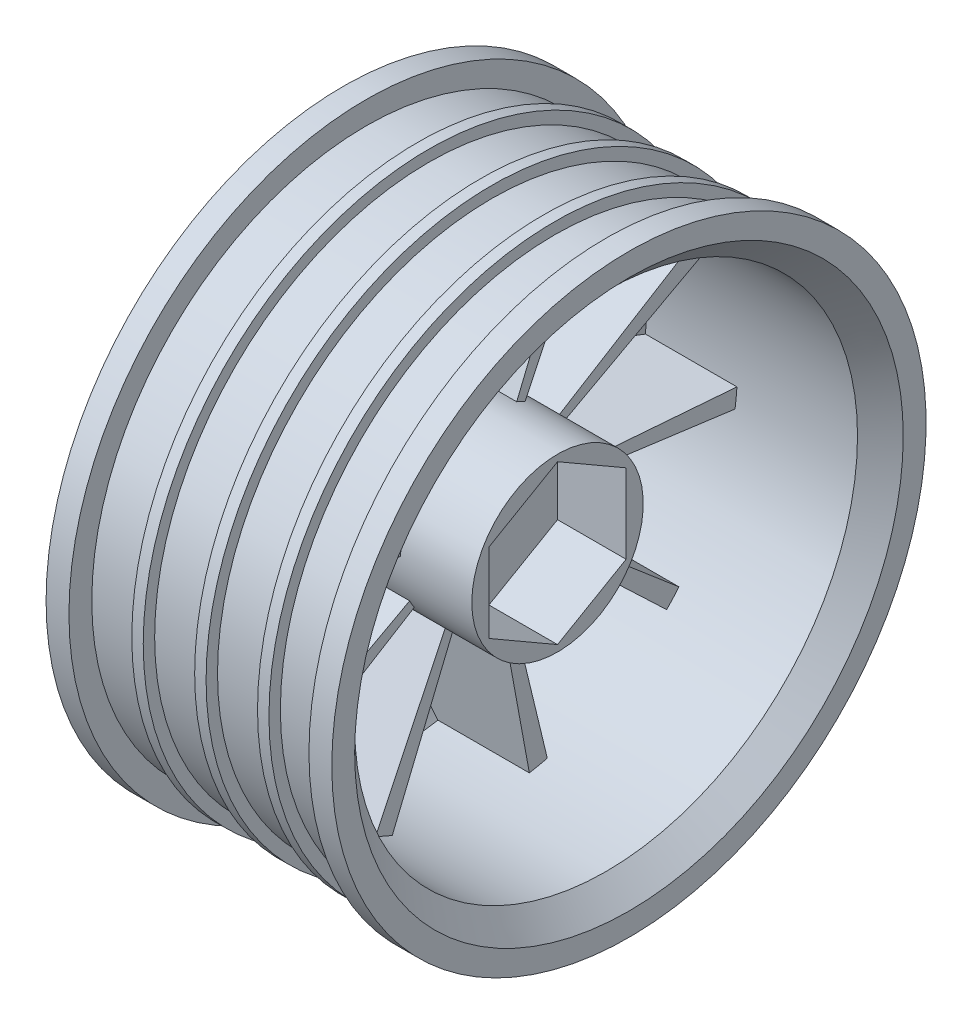
SolidWorks part; units mm, degrees
ref_plane "Front Plane" through (0, 0, 0) normal (0, 0, 1) x (1, 0, 0)
ref_plane "Top Plane" through (0, 0, 0) normal (0, 1, 0) x (1, 0, 0)
ref_plane "Right Plane" through (0, 0, 0) normal (1, 0, 0) x (0, 0, -1)
sketch "Sketch1" plane through (0, 0, 0) normal (0, 1, 0) x (1, 0, 0)
  line L0 (0, 26) -> (-2, 26)
  line L1 (-2, 26) -> (-2, 24)
  line L2 (-2, 24) -> (-6.5, 24)
  line L3 (-6.5, 24) -> (-6.5, 25)
  line L4 (-6.5, 25) -> (-7.5, 25)
  line L5 (-7.5, 25) -> (-7.5, 24)
  line L6 (-7.5, 24) -> (-12, 24)
  line L7 (-12, 24) -> (-12, 25)
  line L8 (-12, 25) -> (-13, 25)
  line L9 (-13, 25) -> (-13, 24)
  line L10 (-13, 24) -> (-17.5, 24)
  line L11 (-17.5, 24) -> (-17.5, 25)
  line L12 (-17.5, 25) -> (-18.5, 25)
  line L13 (-18.5, 25) -> (-18.5, 24)
  line L14 (-18.5, 24) -> (-23, 24)
  line L15 (-23, 24) -> (-23, 26)
  line L16 (-23, 26) -> (-25, 26)
  line L17 (-25, 26) -> (-25, 20)
  line L18 (0, 26) -> (0, 24)
  line L19 (0, 24) -> (-2, 22)
  line L20 (-2, 22) -> (-12.5, 22)
  line L21 (-12.5, 22) -> (-12.5, 7.5)
  line L22 (-12.5, 7.5) -> (-6.25, 7.5)
  line L23 (-6.25, 7.5) -> (-6.25, 0)
  line L24 (-6.25, 0) -> (-18.75, 0)
  line L25 (-19.5583, 5) -> (-19.15, 5)
  line L26 (-18.75, 4.6) -> (-18.75, 0)
  line L27 (0, 0) -> (12.479, 0) construction
  arc A0 (-25, 20) -> (-19.8711, 5.1507) centre (-1.4629, 19.8192) ccw
  arc A1 (-19.5583, 5) -> (-19.8711, 5.1507) centre (-19.5583, 5.4) cw
  arc A2 (-19.15, 5) -> (-18.75, 4.6) centre (-19.15, 4.6) cw
  point P32 (-19.75, 5)
  point P35 (-18.75, 5)
  dimension "D18" = 0.4
  dimension "D1" = 26
  dimension "D2" = 2
  dimension "D3" = 2
  dimension "D4" = 2
  dimension "D5" = 2
  dimension "D6" = 4.5
  dimension "D7" = 1
  dimension "D8" = 1
  dimension "D9" = 2
  dimension "D10" = 6
  dimension "D11" = 7.5
  dimension "D12" = 0
  dimension "D13" = 10.5
  dimension "D14" = 6.25
  dimension "D15" = 5
  dimension "D16" = 1
  dimension "D17" = 12.5
revolve "Revolve1" add sketch "Sketch1" angle 360 about L27
sketch "Sketch2" plane through (-6.25, 0, 0) normal (1, 0, 0) x (0, 0, -1)
  line L1 (0, 6.9282) -> (-6, 3.4641)
  line L2 (-6, 3.4641) -> (-6, -3.4641)
  line L3 (-6, -3.4641) -> (0, -6.9282)
  line L4 (0, -6.9282) -> (6, -3.4641)
  line L5 (6, -3.4641) -> (6, 3.4641)
  line L6 (6, 3.4641) -> (0, 6.9282)
  circle A0 centre (0, 0) radius 6 construction
sketch "Sketch4" plane through (0, 0, 0) normal (1, 0, 0) x (0, 0, -1)
  line L3 (22, 0) -> (6.5454, 1.1951)
  line L4 (6.4657, 1.5704) -> (20.098, 8.9482)
  arc A0 (22, 0) -> (20.098, 8.9482) centre (0, 0) ccw
  arc A1 (6.5454, 1.1951) -> (6.4657, 1.5704) centre (6.5609, 1.3946) cw
  dimension "D1" = 0.2
extrude "Cut-Extrude5" cut sketch "Sketch4" against normal through all
sketch "Sketch5" plane through (-6.25, 0, 0) normal (1, 0, 0) x (0, 0, -1)
  circle A0 centre (0, 0) radius 7.5
extrude "Boss-Extrude1" add sketch "Sketch5" against normal blind 12
ref_axis "Axis2" through (0, 0, 0) along (-1, 0, 0)
pattern_circular "CirPattern3" count 10 over 360 about axis through (0, 0, 0) along (-1, 0, 0) of "Cut-Extrude5"
sketch "Sketch6" plane through (0, 0, 0) normal (1, 0, 0) x (0, 0, -1)
  circle A0 centre (0, 0) radius 24
  circle A1 centre (0, 0) radius 22
extrude "Boss-Extrude3" add sketch "Sketch6" against normal blind 24
chamfer "Chamfer1" distance 2 distance2 2 1 edges at (0, 0, -22)
sketch "Sketch11" plane through (0, 0, 0) normal (0, 1, 0) x (1, 0, 0)
  line L0 (-12.5, 7.5) -> (-18.75, 7.5)
  line L1 (-12.5, 22) -> (-20.5, 22)
  line L2 (-12.5, 7.5) -> (-12.5, 22)
  spline S0 degree 2 poles (-18.75, 7.5) (-24.3963, 14.8634) (-20.5, 22) knots 0 0 0 1 1 1
  dimension "D1" = 7.5
  dimension "D2" = 22
  dimension "D3" = 12.5
  dimension "D4" = 8
  dimension "D5" = 6.25
revolve "Cut-Revolve1" cut sketch "Sketch11" angle 360 about axis through (0, 0, 0) along (-1, 0, 0)
sketch "Sketch13" plane through (-6.25, 0, 0) normal (1, 0, 0) x (0, 0, -1)
  line L0 (7.4902, -0.3824) -> (21.9488, -1.5005)
  line L1 (7.4061, -1.1833) -> (21.7811, -3.0957)
  line L2 (22, 0) -> (7.4147, 1.1279) construction
  line L3 (7.0182, -2.6449) -> (21.5192, -4.5741) construction
  arc A0 (7.4061, -1.1833) -> (7.4902, -0.3824) centre (0, 0) ccw
  arc A1 (21.7811, -3.0957) -> (21.9488, -1.5005) centre (0, 0) ccw
  dimension "D1" = 1.5
  dimension "D2" = 1.5
extrude "Boss-Extrude5" add sketch "Sketch13" against normal up to surface (12.5 mm away) up to face at (-20.8008, -1.5348, -14.7597)
pattern_circular "CirPattern5" count 10 over 360 about axis through (0, 0, 0) along (-1, 0, 0) of "Boss-Extrude5"
sketch "Sketch15" plane through (-6.25, 0, 0) normal (1, 0, 0) x (0, 0, -1)
  circle A0 centre (0, 0) radius 7.5
extrude "Boss-Extrude6" add sketch "Sketch15" against normal blind 11.5
sketch "Sketch14" plane through (-6.25, 0, 0) normal (1, 0, 0) x (0, 0, -1)
  circle A0 centre (0, 0) radius 22
  circle A1 centre (0, 0) radius 7.5
extrude "Cut-Extrude8" cut sketch "Sketch14" against normal blind 6.25
extrude "Cut-Extrude9" cut sketch "Sketch2" against normal blind 6
sketch "Sketch16" plane through (-12.25, 0, 0) normal (1, 0, 0) x (0, 0, -1)
  circle A0 centre (0, 0) radius 2
extrude "Cut-Extrude10" cut sketch "Sketch16" against normal through all
